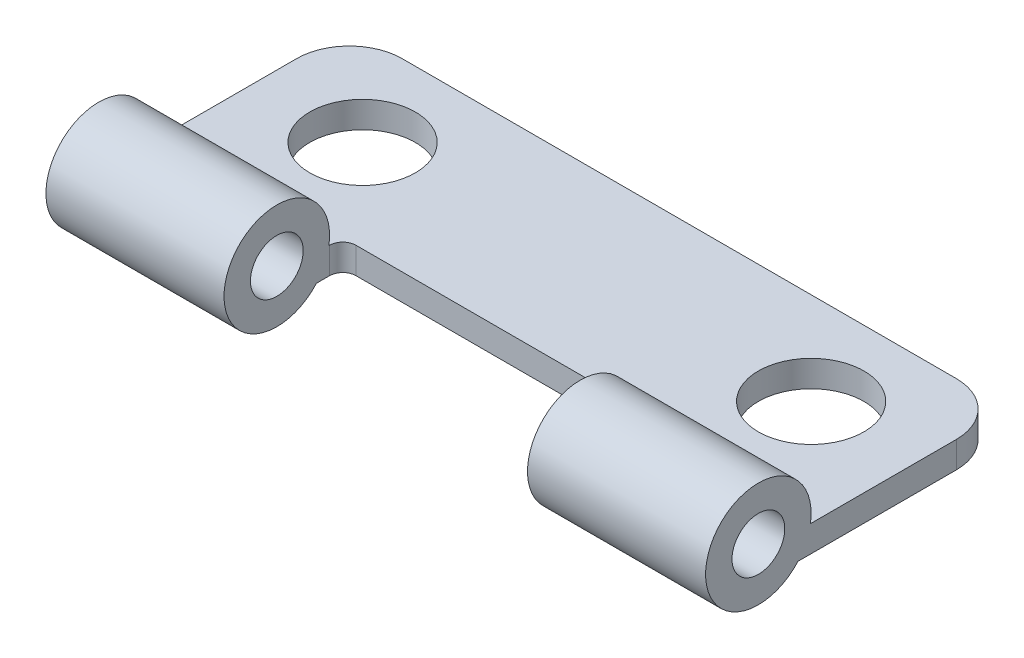
SolidWorks part; units mm, degrees
ref_plane "前视基准面" through (0, 0, 0) normal (0, 0, 1) x (1, 0, 0)
ref_plane "上视基准面" through (0, 0, 0) normal (0, 1, 0) x (1, 0, 0)
ref_plane "右视基准面" through (0, 0, 0) normal (1, 0, 0) x (0, 0, -1)
other "Configuration Table"
sketch "草图1" plane through (0, 0, 0) normal (0, 1, 0) x (1, 0, 0)
  line L0 (-5.75, 0) -> (5.75, 0) construction
  line L1 (-5.75, 0) -> (-5.75, 1)
  line L2 (-5.75, 1) -> (-12.5, 1) construction
  line L3 (-12.5, 1) -> (-12.5, 8)
  line L4 (-12.5, 8) -> (12.5, 8)
  line L5 (12.5, 8) -> (12.5, 1)
  line L6 (12.5, 1) -> (5.75, 1) construction
  line L7 (5.75, 1) -> (5.75, 0)
  line L8 (0, 0) -> (0, 8) construction
  line L9 (-12.5, 1) -> (-12.5, 0)
  line L10 (-12.5, 0) -> (-5.75, 0)
  line L11 (5.75, 0) -> (12.5, 0)
  line L12 (12.5, 0) -> (12.5, 1)
  line L13 (-5.75, 1) -> (5.75, 1)
  line L14 (-12.5, 4.5) -> (12.5, 4.5) construction
  circle A0 centre (-8.5, 4.5) radius 2
  circle A1 centre (8.5, 4.5) radius 2
  point P2 (0, 0)
  dimension "D5" = 4
  dimension "D1" = 25
  dimension "D2" = 7
  dimension "D3" = 1
  dimension "D4" = 11.5
  dimension "D6" = 17
extrude "凸台-拉伸1" add sketch "草图1" along normal blind 1
fillet "圆角1" radius 2 2 edges at (-12.5, 0.5, -8) (12.5, 0.5, -8)
fillet "圆角2" radius 0.5 2 edges at (5.75, 0.5, -1) (-5.75, 0.5, -1)
sketch "草图2" plane through (0, 0, 0) normal (1, 0, 0) x (0, 0, -1)
  line L0 (1, 1) -> (1, 0) construction
  circle A0 centre (-1.5, 1.3229) radius 1
  circle A1 centre (-1.5, 1.3229) radius 2
  dimension "D1" = 4
  dimension "D2" = 2
  dimension "D3" = 2.5
extrude "凸台-拉伸2" add sketch "草图2" against normal up to surface (12.5 mm away) from surface up to face at (-12.5, 0.5, -3) starting at face at (-5.75, 0.5, -0.25)
extrude "凸台-拉伸3" add sketch "草图2<3>" along normal up to surface (12.5 mm away) from surface up to face at (12.5, 0.5, -3) starting at face at (5.75, 0.5, -0.25)
sketch "草图2<3>" plane through (0, 0, 0) normal (1, 0, 0) x (0, 0, -1) same geometry as "草图2"
